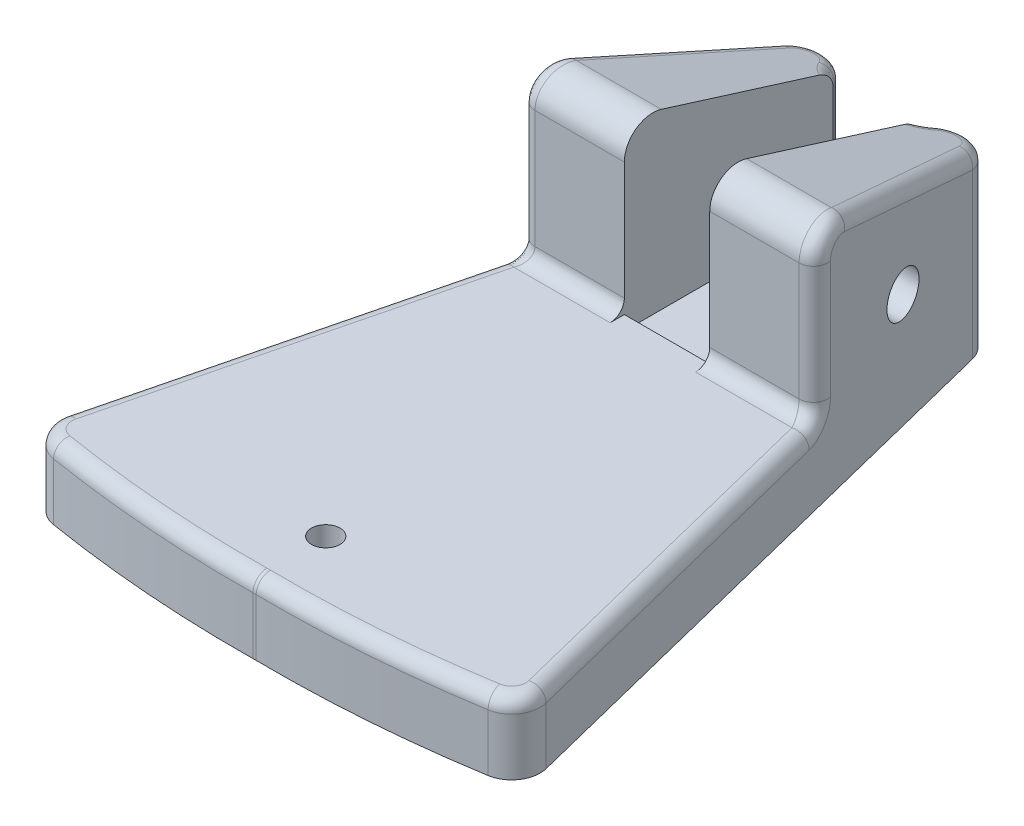
SolidWorks part; units mm, degrees
material "PVC 0.007 Plasticized"
ref_plane "Front Plane" through (0, 0, 0) normal (0, 0, 1) x (1, 0, 0)
ref_plane "Top Plane" through (0, 0, 0) normal (0, 1, 0) x (1, 0, 0)
ref_plane "Right Plane" through (0, 0, 0) normal (1, 0, 0) x (0, 0, -1)
sketch "Sketch1" plane through (0, 0, 0) normal (0, 1, 0) x (1, 0, 0)
  line L0 (0, -26.6303) -> (0, -71.6303) construction
  line L1 (6.9406, -28.1464) -> (16.8849, -68.031)
  line L2 (-6.9406, -28.1464) -> (-16.8849, -68.031)
  line L3 (1.5359, -28.6303) -> (-1.5359, -28.6303)
  arc A0 (-15.2664, -70.4887) -> (-0.1118, -71.6316) centre (-1.0961, 16.3629) ccw
  arc A1 (-16.8849, -68.031) -> (-15.2664, -70.4887) centre (-14.9443, -68.5148) ccw
  arc A2 (-3.2679, -27.6303) -> (-6.9406, -28.1464) centre (-5, -28.6303) ccw
  arc A3 (15.2664, -70.4887) -> (0.1118, -71.6316) centre (1.0961, 16.3629) cw
  arc A4 (16.8849, -68.031) -> (15.2664, -70.4887) centre (14.9443, -68.5148) cw
  arc A5 (3.2679, -27.6303) -> (6.9406, -28.1464) centre (5, -28.6303) cw
  arc A6 (-0.1118, -71.6316) -> (0.1118, -71.6316) centre (0, -81.631) cw
  circle A7 centre (0, -66.6303) radius 1
  arc A8 (3.2679, -27.6303) -> (1.5359, -28.6303) centre (1.5359, -26.6303) cw
  arc A9 (-1.5359, -28.6303) -> (-3.2679, -27.6303) centre (-1.5359, -26.6303) cw
  point P15 (-17.404, -70.1128)
  point P19 (0, -28.6303)
  point P26 (3, -28.6303)
  point P29 (-3, -28.6303)
  dimension "D4" = 2
  dimension "D5" = 88
  dimension "D3" = 2
  dimension "D8" = 10
  dimension "D9" = 2
  dimension "D11" = 2
  dimension "D1" = 14
  dimension "D2" = 45
  dimension "D6" = 3
  dimension "D7" = 43
  dimension "D10" = 5
extrude "Boss-Extrude1" add sketch "Sketch1" along normal blind 5
sketch "Sketch2" plane through (0, 5, 0) normal (0, 1, 0) x (1, 0, 0)
  line L0 (0, -28.6303) -> (0, -42.6497) construction
  line L1 (-3, -27.9928) -> (-3, -42.6497)
  line L2 (3, -27.9928) -> (3, -42.6497)
  line L3 (-10.5567, -42.6497) -> (-3, -42.6497)
  line L4 (-6.9406, -28.1464) -> (-16.8849, -68.031)
  line L5 (16.8849, -68.031) -> (6.9406, -28.1464)
  line L6 (1.5359, -28.6303) -> (-1.5359, -28.6303)
  line L7 (-6.9406, -28.1464) -> (-10.5567, -42.6497)
  line L8 (10.5567, -42.6497) -> (6.9406, -28.1464)
  line L10 (3, -42.6497) -> (10.5567, -42.6497)
  arc A10 (-3.2679, -27.6303) -> (-6.9406, -28.1464) centre (-5, -28.6303) ccw
  arc A11 (-16.8849, -68.031) -> (-15.2664, -70.4887) centre (-14.9443, -68.5148) ccw
  arc A12 (-15.2664, -70.4887) -> (-0.1118, -71.6316) centre (-1.0961, 16.3629) ccw
  arc A13 (0.1118, -71.6316) -> (-0.1118, -71.6316) centre (0, -81.631) ccw
  arc A14 (0.1118, -71.6316) -> (15.2664, -70.4887) centre (1.0961, 16.3629) ccw
  arc A15 (15.2664, -70.4887) -> (16.8849, -68.031) centre (14.9443, -68.5148) ccw
  arc A16 (6.9406, -28.1464) -> (3.2679, -27.6303) centre (5, -28.6303) ccw
  arc A17 (1.5359, -28.6303) -> (3.2679, -27.6303) centre (1.5359, -26.6303) ccw
  arc A18 (-3.2679, -27.6303) -> (-1.5359, -28.6303) centre (-1.5359, -26.6303) ccw
  arc A19 (-3.2679, -27.6303) -> (-6.9406, -28.1464) centre (-5, -28.6303) ccw
  arc A22 (0.1118, -71.6316) -> (-0.1118, -71.6316) centre (0, -81.631) ccw
  arc A25 (6.9406, -28.1464) -> (3.2679, -27.6303) centre (5, -28.6303) ccw
  arc A26 (3, -27.9928) -> (3.2679, -27.6303) centre (1.5359, -26.6303) ccw
  arc A27 (-3.2679, -27.6303) -> (-3, -27.9928) centre (-1.5359, -26.6303) ccw
  point P0 (5.2783, -26.6497)
  dimension "D2" = 6
  dimension "D3" = 16
  dimension "D1" = 0
extrude "Boss-Extrude3" add sketch "Sketch2" along normal blind 12 contours L5 L3 L1 A17 L4 | L2 L10 A13 A14 A15 region at (-5.9201, 5, 35.726) region at (5.9201, 5, 35.726)
sketch "Sketch4" plane through (0, 5, 0) normal (0, 1, 0) x (1, 0, 0)
  line L0 (-3, -42.6497) -> (3, -42.6497)
  line L8 (10.5567, -42.6497) -> (3, -42.6497)
  line L9 (3, -42.6497) -> (3, -27.9928)
  line L10 (1.5359, -28.6303) -> (-1.5359, -28.6303)
  line L11 (-3, -27.9928) -> (-3, -42.6497)
  line L12 (-3, -42.6497) -> (-10.5567, -42.6497)
  line L13 (-10.5567, -42.6497) -> (-16.8849, -68.031)
  line L14 (16.8849, -68.031) -> (10.5567, -42.6497)
  line L16 (3, -42.6497) -> (3, -27.9928)
  line L17 (1.5359, -28.6303) -> (-1.5359, -28.6303)
  line L18 (-3, -27.9928) -> (-3, -42.6497)
  arc A7 (1.5359, -28.6303) -> (3, -27.9928) centre (1.5359, -26.6303) ccw
  arc A8 (-3, -27.9928) -> (-1.5359, -28.6303) centre (-1.5359, -26.6303) ccw
  arc A9 (-16.8849, -68.031) -> (-15.2664, -70.4887) centre (-14.9443, -68.5148) ccw
  arc A10 (-15.2664, -70.4887) -> (-0.1118, -71.6316) centre (-1.0961, 16.3629) ccw
  arc A11 (0.1118, -71.6316) -> (-0.1118, -71.6316) centre (0, -81.631) ccw
  arc A12 (0.1118, -71.6316) -> (15.2664, -70.4887) centre (1.0961, 16.3629) ccw
  arc A13 (15.2664, -70.4887) -> (16.8849, -68.031) centre (14.9443, -68.5148) ccw
  arc A14 (1.5359, -28.6303) -> (3, -27.9928) centre (1.5359, -26.6303) ccw
  arc A15 (-3, -27.9928) -> (-1.5359, -28.6303) centre (-1.5359, -26.6303) ccw
  dimension "D1" = 0
extrude "Cut-Extrude1" cut sketch "Sketch4" against normal blind 1
sketch "Sketch5" plane through (0, 0, 0) normal (1, 0, 0) x (0, 0, -1)
  line L0 (-26.6303, 12) -> (-42.6497, 17)
  line L1 (-26.6303, 0) -> (-26.6303, 17) construction
  line L2 (-42.6497, 17) -> (-42.6497, 21.8133)
  line L3 (-42.6497, 21.8133) -> (-24.9805, 21.8133)
  line L4 (-24.9805, 21.8133) -> (-24.9805, 12)
  line L5 (-24.9805, 12) -> (-26.6303, 12)
  line L6 (-28.1464, 0) -> (-68.031, 0) construction
  circle A0 centre (-34.6303, 8) radius 1.5
  dimension "D2" = 3
  dimension "D1" = 12
  dimension "D3" = 8
  dimension "D4" = 8
extrude "Cut-Extrude2" cut sketch "Sketch5" against normal through all both and the other way through all
fillet "Fillet1" radius 2 2 edges at (6.7783, 17, 42.6497) (-6.7783, 17, 42.6497)
fillet "Fillet3" radius 1 2 edges at (6.7783, 5, 42.6497) (-6.7783, 5, 42.6497)
fillet "Fillet4" radius 1 19 edges at (3.1442, 12.3711, 27.8191) (5.2783, 12.0061, 26.6497) (8.425, 14.3315, 34.1001) (10.3535, 15.8918, 41.8347) (10.5567, 10.1403, 42.6497) (10.6297, 5.2929, 42.9426) (13.8455, 5, 55.8404) (16.6147, 5, 69.6148) (7.7138, 5, 71.3879) (0, 5, 71.631) (-7.7138, 5, 71.3879) (-16.6147, 5, 69.6148) (-13.8455, 5, 55.8404) (-10.6297, 5.2929, 42.9426) (-10.5567, 10.1403, 42.6497) (-10.3535, 15.8918, 41.8347) (-8.425, 14.3315, 34.1001) (-3.1442, 12.3711, 27.8191) (-5.2783, 12.0061, 26.6497)
sketch "Sketch6" plane through (0, 0, 0) normal (0, -1, 0) x (1, 0, 0)
  line L6 (-1.5359, 29.6303) -> (1.5359, 29.6303)
  line L7 (5.9703, 28.3884) -> (15.9146, 68.2729)
  line L8 (-15.9146, 68.2729) -> (-5.9703, 28.3884)
  line L9 (-1.5359, 29.6303) -> (1.5359, 29.6303)
  line L10 (5.9703, 28.3884) -> (15.9146, 68.2729)
  line L11 (-15.9146, 68.2729) -> (-5.9703, 28.3884)
  arc A18 (-5.9703, 28.3884) -> (-4.134, 28.1303) centre (-5, 28.6303) ccw
  arc A19 (-1.5359, 29.6303) -> (-4.134, 28.1303) centre (-1.5359, 26.6303) ccw
  arc A20 (4.134, 28.1303) -> (1.5359, 29.6303) centre (1.5359, 26.6303) ccw
  arc A21 (4.134, 28.1303) -> (5.9703, 28.3884) centre (5, 28.6303) ccw
  arc A22 (15.9146, 68.2729) -> (15.1054, 69.5018) centre (14.9443, 68.5148) ccw
  arc A23 (15.1054, 69.5018) -> (0.123, 70.6317) centre (1.0961, -16.3629) ccw
  arc A24 (-0.123, 70.6317) -> (0.123, 70.6317) centre (0, 81.631) ccw
  arc A25 (-0.123, 70.6317) -> (-15.1054, 69.5018) centre (-1.0961, -16.3629) ccw
  arc A26 (-15.1054, 69.5018) -> (-15.9146, 68.2729) centre (-14.9443, 68.5148) ccw
  arc A27 (-5.9703, 28.3884) -> (-4.134, 28.1303) centre (-5, 28.6303) ccw
  arc A28 (-1.5359, 29.6303) -> (-4.134, 28.1303) centre (-1.5359, 26.6303) ccw
  arc A29 (4.134, 28.1303) -> (1.5359, 29.6303) centre (1.5359, 26.6303) ccw
  arc A30 (4.134, 28.1303) -> (5.9703, 28.3884) centre (5, 28.6303) ccw
  arc A31 (15.9146, 68.2729) -> (15.1054, 69.5018) centre (14.9443, 68.5148) ccw
  arc A32 (15.1054, 69.5018) -> (0.123, 70.6317) centre (1.0961, -16.3629) ccw
  arc A33 (-0.123, 70.6317) -> (0.123, 70.6317) centre (0, 81.631) ccw
  arc A34 (-0.123, 70.6317) -> (-15.1054, 69.5018) centre (-1.0961, -16.3629) ccw
  arc A35 (-15.1054, 69.5018) -> (-15.9146, 68.2729) centre (-14.9443, 68.5148) ccw
  dimension "D1" = 1
extrude "Cut-Extrude3" cut sketch "Sketch6" against normal blind 1
